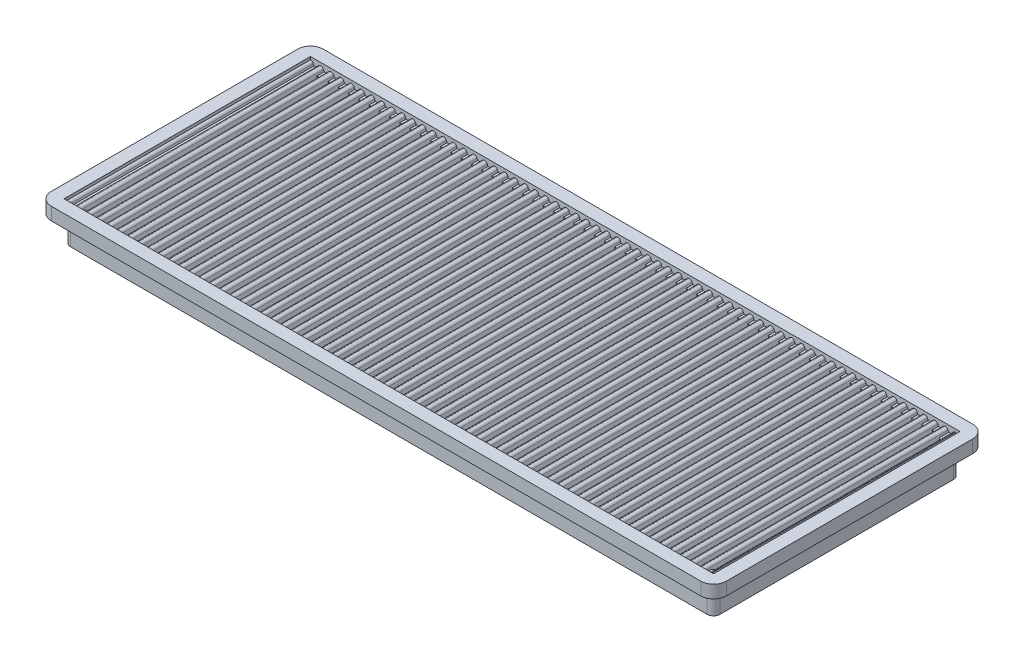
SolidWorks part; units mm, degrees
ref_plane "Front Plane" through (0, 0, 0) normal (0, 0, 1) x (1, 0, 0)
ref_plane "Top Plane" through (0, 0, 0) normal (0, 1, 0) x (1, 0, 0)
ref_plane "Right Plane" through (0, 0, 0) normal (1, 0, 0) x (0, 0, -1)
sketch "Sketch1" plane through (0, 0, 0) normal (0, 1, 0) x (1, 0, 0)
  line L0 (6.35, 128.6002) -> (328.6252, 128.6002)
  line L1 (6.35, 0) -> (328.6252, 0)
  line L2 (0, 6.35) -> (0, 128.6002)
  line L3 (6.35, 134.9502) -> (328.6252, 134.9502)
  line L4 (334.9752, 6.35) -> (334.9752, 128.6002)
  line L5 (328.6252, 6.35) -> (328.6252, 128.6002)
  line L6 (6.35, 6.35) -> (328.6252, 6.35)
  line L7 (6.35, 6.35) -> (6.35, 128.6002)
  line L8 (334.9752, 0) -> (334.9752, 134.9502) construction
  line L9 (0, 0) -> (334.9752, 0) construction
  line L10 (0, 134.9502) -> (334.9752, 134.9502) construction
  line L11 (0, 0) -> (0, 134.9502) construction
  arc A0 (334.9752, 6.35) -> (328.6252, 0) centre (328.6252, 6.35) cw
  arc A1 (328.6252, 134.9502) -> (334.9752, 128.6002) centre (328.6252, 128.6002) cw
  arc A2 (6.35, 134.9502) -> (0, 128.6002) centre (6.35, 128.6002) ccw
  arc A3 (0, 6.35) -> (6.35, 0) centre (6.35, 6.35) ccw
  dimension "D4" = 6.35
  dimension "D1" = 134.9502
  dimension "D2" = 334.9752
  dimension "D3" = 6.35
extrude "Boss-Extrude1" add sketch "Sketch1" along normal blind 6.35
sketch "Sketch2" plane through (0, 0, -128.6002) normal (0, 0, 1) x (1, 0, 0)
  line L0 (11.43, 4.927) -> (11.43, 10.1352) construction
  line L1 (6.35, 6.35) -> (6.35, 0) construction
  line L2 (11.43, 4.927) -> (14.5755, 4.927) construction
  arc A0 (6.35, 4.927) -> (7.7454, 3.9622) centre (6.35, 3.4355) cw
  arc A1 (7.7454, 3.9622) -> (8.5387, 2.1375) centre (26.6749, 11.1068) ccw
  arc A2 (8.5387, 2.1375) -> (9.4267, 2.1427) centre (8.9814, 2.3565) ccw
  arc A3 (9.4267, 2.1427) -> (10.1321, 3.9622) centre (-1.918, 7.5878) ccw
  arc A4 (10.1321, 3.9622) -> (11.43, 4.927) centre (11.43, 3.5717) cw
  dimension "D1" = 5.08
extrude "Extrude-Thin1" add sketch "Sketch2" along normal up to surface (122.2502 mm away) thin
pattern_linear "LPattern3" count 63 spacing 5.08 along (1, 0, 0) of "Extrude-Thin1"
sketch "Sketch3" plane through (0, 0, 0) normal (0, -1, 0) x (1, 0, 0)
  line L1 (6.35, -6.35) -> (328.6252, -6.35)
  line L2 (6.35, -6.35) -> (6.35, -128.6002)
  line L3 (6.35, -128.6002) -> (328.6252, -128.6002)
  line L4 (328.6252, -6.35) -> (328.6252, -128.6002)
  line L8 (15.875, -9.525) -> (319.1002, -9.525)
  line L9 (325.4502, -15.875) -> (325.4502, -119.0752)
  line L10 (15.875, -125.4252) -> (319.1002, -125.4252)
  line L11 (9.525, -15.875) -> (9.525, -119.0752)
  line L12 (328.6252, -6.35) -> (6.35, -6.35)
  line L13 (6.35, -6.35) -> (6.35, -128.6002)
  line L14 (6.35, -128.6002) -> (328.6252, -128.6002)
  line L15 (328.6252, -128.6002) -> (328.6252, -6.35)
  line L16 (328.6252, -6.35) -> (6.35, -6.35)
  line L17 (6.35, -6.35) -> (6.35, -128.6002)
  line L18 (6.35, -128.6002) -> (328.6252, -128.6002)
  line L19 (328.6252, -128.6002) -> (328.6252, -6.35)
  line L20 (9.525, -9.525) -> (9.525, -125.4252) construction
  line L21 (9.525, -125.4252) -> (325.4502, -125.4252) construction
  line L22 (325.4502, -9.525) -> (325.4502, -125.4252) construction
  line L23 (9.525, -9.525) -> (325.4502, -9.525) construction
  arc A4 (9.525, -119.0752) -> (15.875, -125.4252) centre (15.875, -119.0752) ccw
  arc A5 (319.1002, -125.4252) -> (325.4502, -119.0752) centre (319.1002, -119.0752) ccw
  arc A6 (319.1002, -9.525) -> (325.4502, -15.875) centre (319.1002, -15.875) cw
  arc A7 (15.875, -9.525) -> (9.525, -15.875) centre (15.875, -15.875) ccw
  line M13 (328.6252, -128.6002) -> (6.35, -128.6002)
  line M14 (6.35, -128.6002) -> (6.35, -6.35)
  line M15 (6.35, -6.35) -> (328.6252, -6.35)
  line M16 (328.6252, -6.35) -> (328.6252, -128.6002)
  dimension "D3" = 6.35
  dimension "D1" = 6.35
  dimension "D2" = 3.175
extrude "Boss-Extrude2" add sketch "Sketch3" along normal blind 12.7 and the other way blind 3.175 contours A7 L8 A6 L9 A5 L10 A4 L11 M13 M16 M15 M14
fillet "Fillet1" radius 3.175 8 edges at (167.4876, 0, -6.35) (6.35, 0, -67.4751) (328.6252, 0, -67.4751) (6.35, -6.35, -6.35) (6.35, -6.35, -128.6002) (328.6252, -6.35, -128.6002) (167.4876, 0, -128.6002) (328.6252, -6.35, -6.35)
